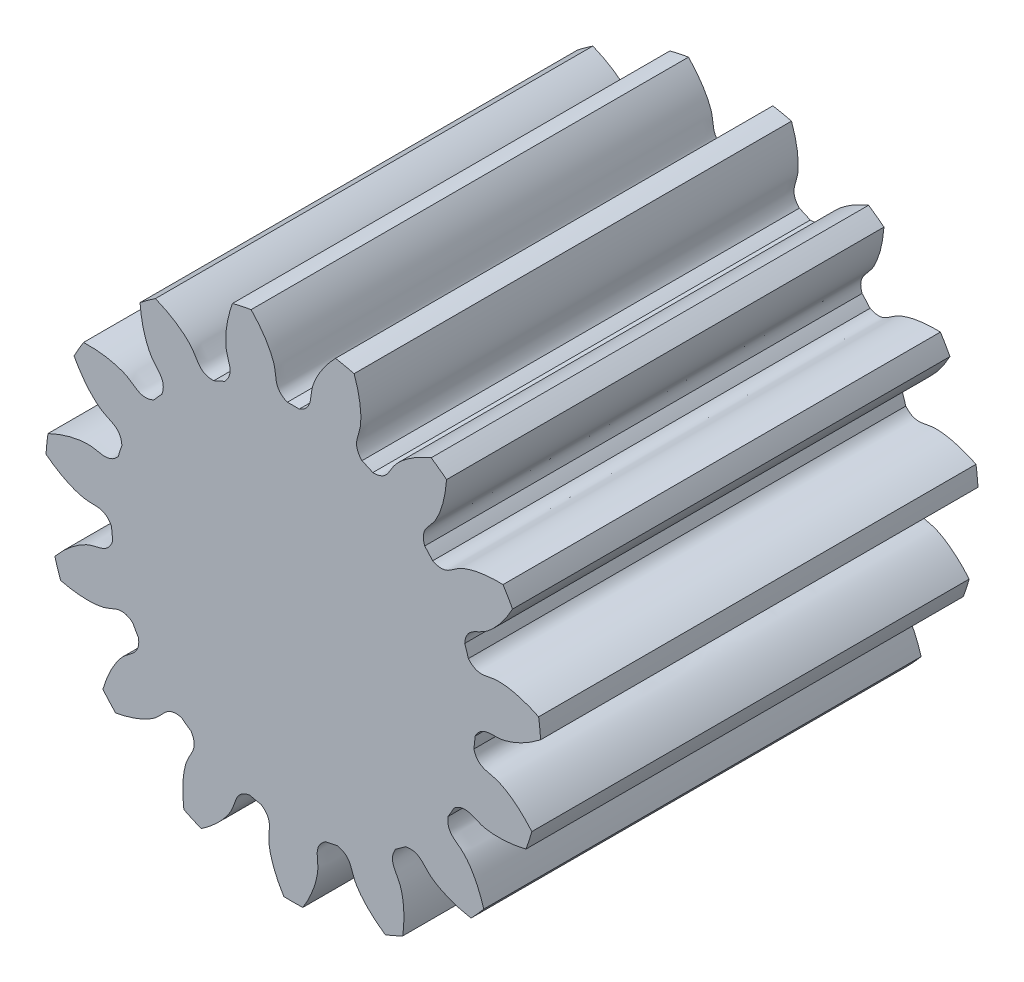
SolidWorks part; units mm, degrees
ref_plane "前视基准面" through (0, 0, 0) normal (0, 0, 1) x (1, 0, 0)
ref_plane "上视基准面" through (0, 0, 0) normal (0, 1, 0) x (1, 0, 0)
ref_plane "右视基准面" through (0, 0, 0) normal (1, 0, 0) x (0, 0, -1)
sketch "草图1" plane through (0, 0, 0) normal (0, 0, 1) x (1, 0, 0)
  circle A0 centre (0, 0) radius 17
extrude "凸台-拉伸1" add sketch "草图1" along normal blind 30
ref_axis "基准轴1" through (0, 0, -1.5) along (0, 0, 1)
sketch "草图2" plane through (0, 0, 0) normal (0, 0, 1) x (1, 0, 0)
  line L0 (0, 0) -> (0, 17) construction
  circle A0 centre (0, 0) radius 17 construction
  arc A1 (0.4086, 12.4933) -> (-0.4086, 12.4933) centre (0, 0) ccw
  arc A2 (6.4937, 19.2719) -> (-6.4937, 19.2719) centre (0, 0) ccw
  spline S0 degree 3 poles (0.4086, 12.4933) (1.3144, 12.8688) (1.1442, 13.5727) (1.3025, 14.217) (1.3149, 14.2633) (1.3297, 14.3148) (1.3472, 14.3713) (1.3676, 14.4329) (1.3912, 14.4993) (1.418, 14.5705) (1.4484, 14.6465) (1.4824, 14.7269) (1.5204, 14.8119) (1.5624, 14.9011) (1.6088, 14.9946) (1.6596, 15.0921) (1.715, 15.1935) (1.7753, 15.2987) (1.8405, 15.4075) (1.9109, 15.5198) (1.9867, 15.6353) (2.0679, 15.754) (2.1547, 15.8755) (2.2473, 15.9999) (2.3459, 16.1268) (2.4505, 16.2561) (2.5613, 16.3877) (2.6784, 16.5212) (2.802, 16.6565) (2.9322, 16.7934) (3.069, 16.9316) (3.2126, 17.0711) (3.3631, 17.2115) (3.5206, 17.3526) (3.6851, 17.4942) (3.8568, 17.6361) (4.0357, 17.778) (4.2219, 17.9197) (4.4154, 18.061) (4.6163, 18.2017) (4.8247, 18.3414) (5.0406, 18.48) (5.2641, 18.6172) (5.4951, 18.7527) (5.7336, 18.8864) (6.0652, 19.0635) (6.3203, 19.1901) (6.4937, 19.2719) knots 0 0 0 0 0.202473 0.206979 0.212085 0.217793 0.224101 0.23101 0.23852 0.24663 0.255341 0.264653 0.274566 0.285079 0.296194 0.307909 0.320225 0.333141 0.346659 0.360777 0.375496 0.390816 0.406736 0.423257 0.440379 0.458102 0.476426 0.49535 0.514875 0.535001 0.555728 0.577055 0.598984 0.621513 0.644642 0.668373 0.692704 0.717636 0.743169 0.769303 0.796037 0.823373 0.851309 0.879845 0.908983 0.938721 1 1 1 1
  spline S1 degree 3 poles (-0.4086, 12.4933) (-1.3144, 12.8688) (-1.1442, 13.5727) (-1.3025, 14.217) (-1.3149, 14.2633) (-1.3297, 14.3148) (-1.3472, 14.3713) (-1.3676, 14.4329) (-1.3912, 14.4993) (-1.418, 14.5705) (-1.4484, 14.6465) (-1.4824, 14.7269) (-1.5204, 14.8119) (-1.5624, 14.9011) (-1.6088, 14.9946) (-1.6596, 15.0921) (-1.715, 15.1935) (-1.7753, 15.2987) (-1.8405, 15.4075) (-1.9109, 15.5198) (-1.9867, 15.6353) (-2.0679, 15.754) (-2.1547, 15.8755) (-2.2473, 15.9999) (-2.3459, 16.1268) (-2.4505, 16.2561) (-2.5613, 16.3877) (-2.6784, 16.5212) (-2.802, 16.6565) (-2.9322, 16.7934) (-3.069, 16.9316) (-3.2126, 17.0711) (-3.3631, 17.2115) (-3.5206, 17.3526) (-3.6851, 17.4942) (-3.8568, 17.6361) (-4.0357, 17.778) (-4.2219, 17.9197) (-4.4154, 18.061) (-4.6163, 18.2017) (-4.8247, 18.3414) (-5.0406, 18.48) (-5.2641, 18.6172) (-5.4951, 18.7527) (-5.7336, 18.8864) (-6.0652, 19.0635) (-6.3203, 19.1901) (-6.4937, 19.2719) knots 0 0 0 0 0.202473 0.206979 0.212085 0.217793 0.224101 0.23101 0.23852 0.24663 0.255341 0.264653 0.274566 0.285079 0.296194 0.307909 0.320225 0.333141 0.346659 0.360777 0.375496 0.390816 0.406736 0.423257 0.440379 0.458102 0.476426 0.49535 0.514875 0.535001 0.555728 0.577055 0.598984 0.621513 0.644642 0.668373 0.692704 0.717636 0.743169 0.769303 0.796037 0.823373 0.851309 0.879845 0.908983 0.938721 1 1 1 1
extrude "切除-拉伸1" cut sketch "草图2" along normal through all
pattern_circular "阵列(圆周)1" count 15 every 24 about axis through (0, 0, -1.5) along (0, 0, 1) of "切除-拉伸1"
sketch "草图3" plane through (0, 0, 0) normal (0, 0, 1) x (1, 0, 0)
  circle A0 centre (0, 0) radius 15 construction
  dimension "Dn" = 30
